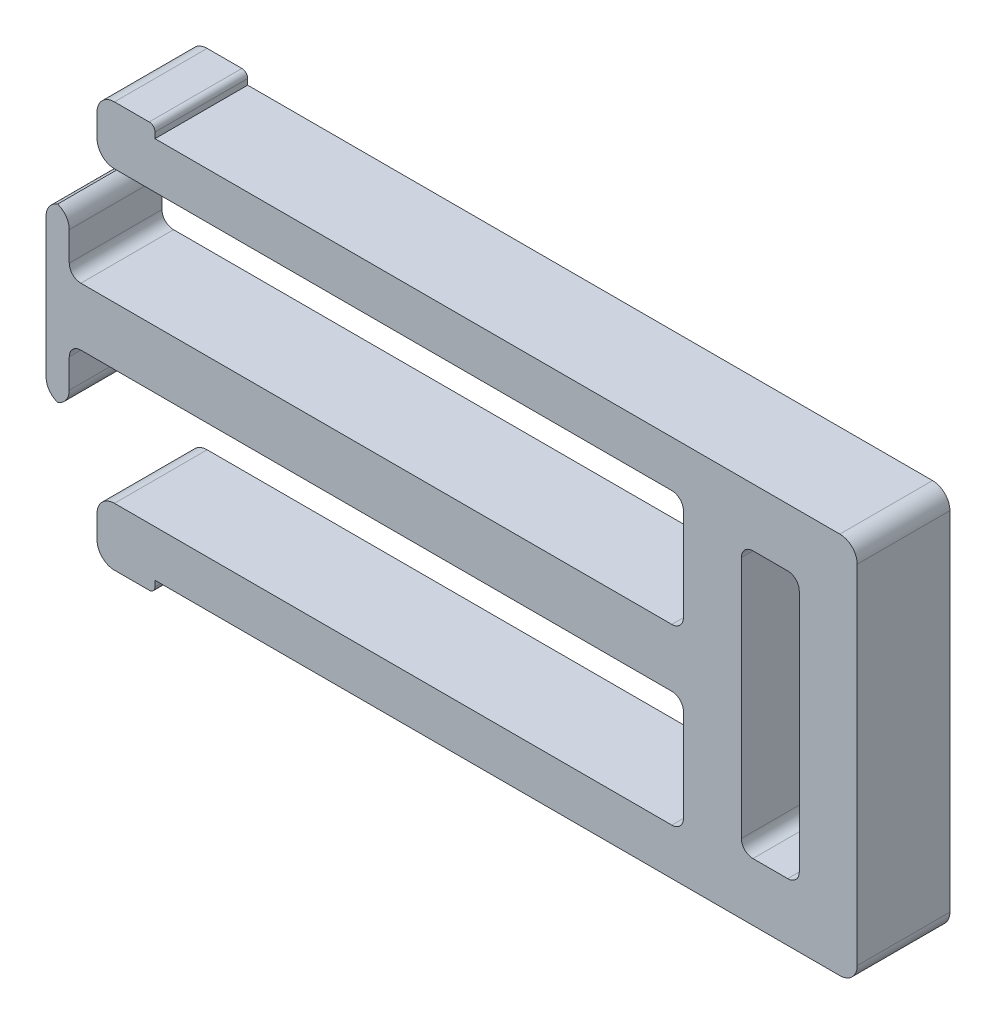
SolidWorks part; units mm, degrees
ref_plane "Front Plane" through (0, 0, 0) normal (1, 0, 0) x (0, 1, 0)
ref_plane "Top Plane" through (0, 0, 0) normal (0, 0, 1) x (0, 1, 0)
ref_plane "Right Plane" through (0, 0, 0) normal (0, 1, 0) x (-1, 0, 0)
sketch "Sketch1" plane through (0, 0, 0) normal (0, 0, 1) x (0, 1, 0)
  line L1 (0, 0) -> (-33, 0)
  line L3 (-5, 5) -> (-28, 5)
  line L8 (-28, 5) -> (-28, 10)
  line L12 (-5, 5) -> (-5, 10)
  line L13 (-28, 10) -> (-5, 10)
  line L15 (-29, 15) -> (-19, 15)
  line L19 (-33, 60.6) -> (-34, 60.6)
  line L20 (-34, 60.6) -> (-34, 65.6)
  line L21 (-34, 65.6) -> (-29, 65.6)
  line L22 (-29, 65.6) -> (-29, 15)
  line L23 (-4, 15) -> (-4, 65.6)
  line L24 (-4, 65.6) -> (1, 65.6)
  line L25 (1, 65.6) -> (1, 60.6)
  line L26 (1, 60.6) -> (0, 60.6)
  line L28 (-24, 70) -> (-9, 70)
  line L29 (-19, 68) -> (-19, 15)
  line L32 (-14, 68) -> (-14, 15)
  line L33 (-16.5, 10) -> (-16.5, 70) construction
  line L34 (-33, 60.6) -> (-33, 0)
  line L36 (-24, 70) -> (-24, 68)
  line L37 (-24, 68) -> (-19, 68)
  line L38 (-14, 15) -> (-4, 15)
  line L39 (-14, 68) -> (-9, 68)
  line L40 (-9, 68) -> (-9, 70)
  line L42 (0, 60.6) -> (0, 0)
  dimension "D1" = 33
  dimension "D5" = 5
  dimension "D2" = 5
  dimension "D6" = 5
  dimension "D11" = 5
  dimension "D12" = 5
  dimension "D13" = 50.6
  dimension "D14" = 50.6
  dimension "D16" = 2
  dimension "D17" = 15
  dimension "D15" = 5
  dimension "D18" = 2.5
  dimension "D19" = 7.5
  dimension "D20" = 55
  dimension "D3" = 5
  dimension "D4" = 5
  dimension "D7" = 4
  dimension "D8" = 4
  dimension "D9" = 1
  dimension "D10" = 1
extrude "Boss-Extrude2" add sketch "Sketch1" along normal blind 8
fillet "Fillet1" radius 1 10 edges at (-68, -19, 4) (-68, -14, 4) (-15, -4, 4) (-15, -19, 4) (-5, -28, 4) (-5, -5, 4) (-10, -5, 4) (-10, -28, 4) (-15, -14, 4) (-15, -29, 4)
fillet "Fillet2" radius 0.5 2 edges at (-60.6, 1, 4) (-60.6, -34, 4)
fillet "Fillet3" radius 1.5 10 edges at (-70, -24, 4) (-70, -9, 4) (0, -33, 4) (0, 0, 4) (-68, -9, 4) (-68, -24, 4) (-65.6, 1, 4) (-65.6, -4, 4) (-65.6, -29, 4) (-65.6, -34, 4)
equation "\"b\"= 8"
equation "\"h\"= 4"
equation "\"L\"= 50.6"
equation "\"Llip\"= 5"
equation "\"beamL\"= \"L\" - \"Llip\""
equation "\"hlip\"= 1"
equation "\"gap\"= 25"
equation "\"RootFillet\"= 1"
equation "\"D1@Sketch1\"= \"gap\"+2* \"h\""
equation "\"D11@Sketch1\"=\"Llip\""
equation "\"D12@Sketch1\"=\"Llip\""
equation "\"D13@Sketch1\"=\"L\""
equation "\"D14@Sketch1\"=\"L\""
equation "\"D7@Sketch1\"=\"h\""
equation "\"D8@Sketch1\"=\"h\""
equation "\"D9@Sketch1\"=\"hlip\""
equation "\"D10@Sketch1\"=\"hlip\""
equation "\"D1@Boss-Extrude2\"=\"b\""
